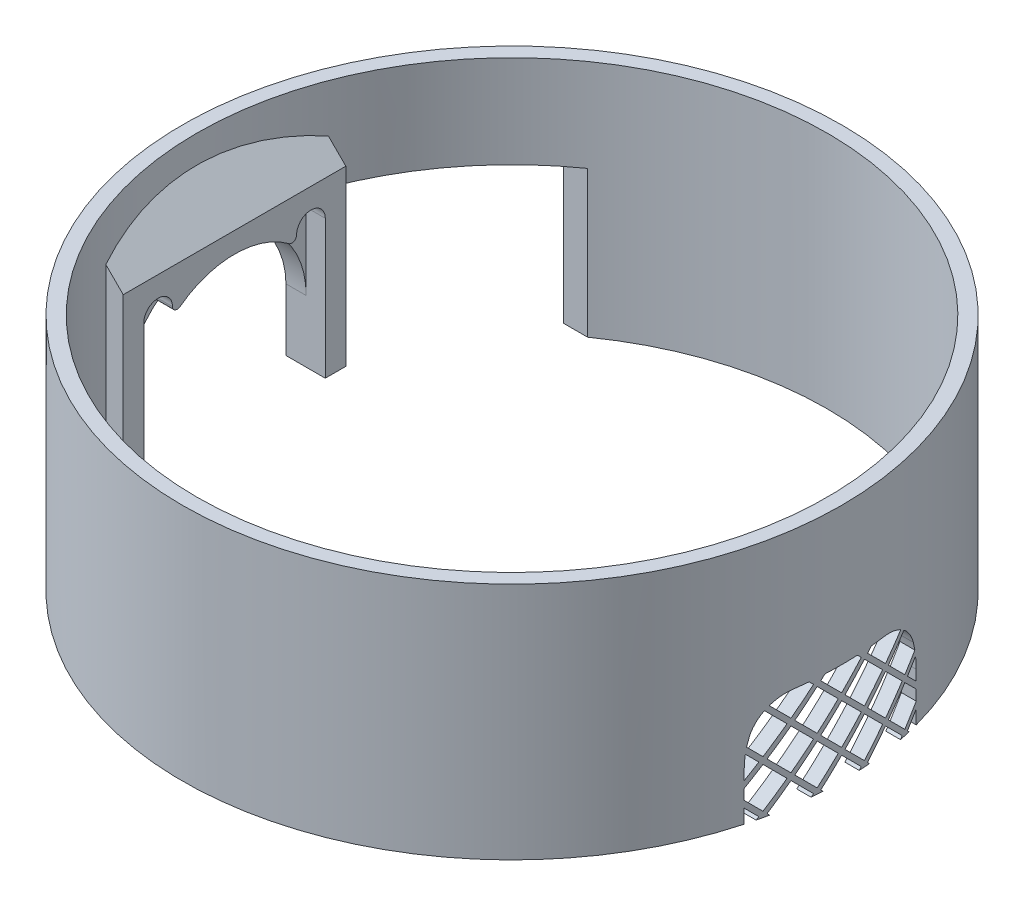
SolidWorks part; units mm, degrees
ref_plane "Front Plane" through (0, 0, 0) normal (0, 0, 1) x (1, 0, 0)
ref_plane "Top Plane" through (0, 0, 0) normal (0, 1, 0) x (1, 0, 0)
ref_plane "Right Plane" through (0, 0, 0) normal (1, 0, 0) x (0, 0, -1)
sketch "Sketch1" plane through (0, 0, 0) normal (0, 1, 0) x (1, 0, 0)
  circle A0 centre (0, 0) radius 69
  circle A1 centre (0, 0) radius 66
  dimension "D1" = 138
  dimension "D2" = 3
extrude "Boss-Extrude1" add sketch "Sketch1" along normal blind 50
sketch "Sketch4" plane through (0, 0, 0) normal (1, 0, 0) x (0, 0, -1)
  line L1 (23.3, 0) -> (53.9, 0)
  line L2 (23.3, 0) -> (23.3, 30.6)
  line L3 (23.3, 30.6) -> (53.9, 30.6)
  line L4 (53.9, 0) -> (53.9, 30.6)
  dimension "D1" = 30.6
  dimension "D2" = 30.6
  dimension "D3" = 0
  dimension "D4" = 23.3
extrude "Cut-Extrude2" cut sketch "Sketch4" against normal through all
sketch "Sketch5" plane through (0, 0, 0) normal (1, 0, 0) x (0, 0, -1)
  line L8 (19, 13) -> (19, -6)
  line L9 (19, -6) -> (-19, -6)
  line L10 (-19, -6) -> (-19, 13)
  arc A1 (19, 13) -> (-19, 13) centre (0, 13) ccw
  dimension "D1" = 19
  dimension "D3" = 13
  dimension "D2" = 19
extrude "Cut-Extrude6" cut sketch "Sketch5" against normal through all
sketch "Sketch6" plane through (0, 0, 0) normal (1, 0, 0) x (0, 0, -1)
  line L0 (19, 13) -> (19, 0)
  line L2 (-19, 0) -> (-19, 13)
  line L3 (23.3, 13) -> (23.3, 0)
  line L4 (-23.3, 0) -> (-23.3, 13)
  line L5 (23.3, 0) -> (19, 0)
  line L6 (-19, 0) -> (-23.3, 0)
  arc A0 (19, 13) -> (-19, 13) centre (0, 13) ccw
  arc A1 (23.3, 13) -> (-23.3, 13) centre (0, 13) ccw
  dimension "D1" = 19
  dimension "D3" = 0
  dimension "D2" = 4.3
extrude "Boss-Extrude2" add sketch "Sketch6" against normal up to next from offset 58.1 offset against normal yes
sketch "Sketch7" plane through (-58.1, 0, 0) normal (1, 0, 0) x (0, 0, -1)
  line L0 (0, 36.3) -> (15, 36.3) construction
  arc A0 (23.3, 13) -> (-23.3, 13) centre (0, 13) ccw construction
  dimension "D1" = 15
ref_plane "Plane2" through (-10.9, -10.9, 0) normal (-0.7071, -0.7071, 0) x (0, 0, -1)
sketch "Sketch8" plane through (-10.9, -10.9, 0) normal (-0.7071, -0.7071, 0) x (0, 0, -1)
  line L0 (23.3, -41.0829) -> (23.3, -50.2753) construction
  line L1 (-23.3, -84.0829) -> (23.3, -84.0829)
  line L2 (-23.3, -84.0829) -> (-23.3, -49.0829)
  line L3 (-23.3, -49.0829) -> (23.3, -49.0829)
  line L4 (23.3, -84.0829) -> (23.3, -49.0829)
  line L5 (-23.3, -50.2753) -> (-23.3, -41.0829) construction
  line L6 (19, -41.0829) -> (23.3, -41.0829) construction
  dimension "D1" = 0
  dimension "D2" = 0
  dimension "D3" = 8
  dimension "D4" = 35
extrude "Boss-Extrude4" add sketch "Sketch8" along normal blind 30 contours L2 L1 L4 L3
sketch "Sketch9" plane through (0, 0, 0) normal (0, -1, 0) x (1, 0, 0)
  line L0 (-58.1, -23.3) -> (-61.7504, -23.3)
  line L1 (-64.947, -23.3) -> (-58.1, -23.3) construction
  line L6 (-38.0892, -53.9) -> (-43.0789, -53.9)
  line L7 (-38.0892, -53.9) -> (-43.0789, -53.9)
  line L12 (-66.3325, 19) -> (-58.1, 19)
  line L14 (-58.1, 19) -> (-58.1, 23.3)
  line L15 (-58.1, 23.3) -> (-61.7504, 23.3)
  line L18 (-58.1, 19) -> (-58.1, 23.3)
  line L19 (-58.1, 23.3) -> (-61.7504, 23.3)
  line L20 (-58.1, 19) -> (-58.1, -19)
  line L24 (-58.1, -19) -> (-66.3325, -19)
  line L25 (-64.947, -23.3) -> (-58.1, -23.3)
  line L27 (-58.1, -23.3) -> (-58.1, -19)
  line L31 (-58.1, -23.3) -> (-58.1, -19)
  arc A6 (-43.0789, -53.9) -> (-66.3325, 19) centre (0, 0) ccw
  arc A7 (-38.0892, -53.9) -> (-61.7504, 23.3) centre (0, 0) ccw
  arc A8 (-43.0789, -53.9) -> (-66.3325, 19) centre (0, 0) ccw
  arc A9 (-38.0892, -53.9) -> (-61.7504, 23.3) centre (0, 0) ccw
  arc A10 (-66.3325, -19) -> (-66.3325, 19) centre (0, 0) ccw
  arc A11 (-61.7504, -23.3) -> (-61.7504, 23.3) centre (0, 0) ccw
  arc A12 (-66.3325, -19) -> (-64.947, -23.3) centre (0, 0) ccw
  arc A14 (-66.3325, -19) -> (-64.947, -23.3) centre (0, 0) ccw
  circle A16 centre (0, 0) radius 69
  arc A18 (-61.7504, -23.3) -> (-61.7504, 23.3) centre (0, 0) ccw
  line M15 (-66.3325, 19) -> (-58.1, 19)
  line M16 (-58.1, 19) -> (-58.1, 23.3)
  line M17 (-58.1, 23.3) -> (-61.7504, 23.3)
  arc M18 (-61.7504, 23.3) -> (-38.0892, -53.9) centre (0, 0) cw
  dimension "D1" = 0
  dimension "D2" = 0
extrude "Cut-Extrude7" cut sketch "Sketch9" against normal through all flip side to cut contours A16
extrude "Cut-Extrude8" cut sketch "Sketch9<3>" against normal through all contours L31 A11 M15 M18 M17 M16 region at (1.3919, 0, 0)
sketch "Sketch9<3>" plane through (0, 0, 0) normal (0, -1, 0) x (1, 0, 0) same geometry as "Sketch9"
extrude "Cut-Extrude9" cut sketch "Sketch5<2>" against normal through all
sketch "Sketch5<2>" plane through (0, 0, 0) normal (1, 0, 0) x (0, 0, -1) same geometry as "Sketch5"
sketch "Sketch11" plane through (-58.1, 0, 0) normal (1, 0, 0) x (0, 0, -1)
  line L0 (-19, 29) -> (-19, 11)
  line L1 (-19, 0) -> (-19, 13) construction
  line L2 (-19, 11) -> (-13, 11)
  line L3 (-13, 11) -> (-13, 29)
  line L4 (13, 29) -> (13, 11)
  line L5 (19, 29) -> (19, 11)
  line L6 (19, 13) -> (19, 0) construction
  line L7 (13, 11) -> (19, 11)
  arc A0 (19, 29) -> (13, 29) centre (16, 29) ccw
  arc A1 (-13, 29) -> (-19, 29) centre (-16, 29) ccw
  dimension "D1" = 6
  dimension "D2" = 6
  dimension "D3" = 18
  dimension "D4" = 18
extrude "Cut-Extrude11" cut sketch "Sketch11" against normal blind 4
fillet "Fillet3" radius 1 2 edges at (-60.1, 26.8564, -13) (-60.1, 26.8564, 13)
sketch "Sketch12" plane through (0, 0, 0) normal (1, 0, 0) x (0, 0, -1)
  line L0 (0, -0.9) -> (0, 0) construction
  line L1 (-69, 0) -> (69, 0) construction
  line L25 (-18, -0.9) -> (18, -0.9)
  line L28 (18, -0.9) -> (18, 10.1)
  line L29 (9.5394, 21.1) -> (-9.5394, 21.1)
  line L30 (-18, 10.1) -> (-18, -0.9)
  line L31 (18, -0.9) -> (18, 10.1)
  line L32 (9.5394, 21.1) -> (-9.5394, 21.1)
  line L33 (-18, 10.1) -> (-18, -0.9)
  line L51 (14.2005, -0.9) -> (14.8492, -0.2513)
  line L52 (14.8492, -0.2513) -> (15.498, -0.9)
  line L54 (16.9122, -0.9) -> (15.5563, 0.4558)
  line L55 (15.5563, 0.4558) -> (18, 2.8995)
  line L71 (4.301, -0.9) -> (4.9497, -0.2513)
  line L72 (4.9497, -0.2513) -> (5.5985, -0.9)
  line L73 (14.1421, 0.4558) -> (12.7863, -0.9)
  line L74 (7.0127, -0.9) -> (5.6569, 0.4558)
  line L75 (5.6569, 0.4558) -> (9.8995, 4.6985)
  line L76 (9.8995, 4.6985) -> (14.1421, 0.4558)
  line L77 (18, 4.3137) -> (14.8492, 1.163)
  line L78 (14.8492, 1.163) -> (10.6066, 5.4056)
  line L79 (10.6066, 5.4056) -> (14.8492, 9.6482)
  line L80 (14.8492, 9.6482) -> (18, 6.4975)
  line L82 (18, 7.9117) -> (15.5563, 10.3553)
  line L83 (15.5563, 10.3553) -> (17.8225, 12.6215)
  line L91 (-5.5985, -0.9) -> (-4.9497, -0.2513)
  line L92 (-4.9497, -0.2513) -> (-4.301, -0.9)
  line L93 (4.2426, 0.4558) -> (2.8868, -0.9)
  line L94 (-2.8868, -0.9) -> (-4.2426, 0.4558)
  line L95 (-4.2426, 0.4558) -> (0, 4.6985)
  line L96 (0, 4.6985) -> (4.2426, 0.4558)
  line L97 (9.1924, 5.4056) -> (4.9497, 1.163)
  line L98 (4.9497, 1.163) -> (0.7071, 5.4056)
  line L99 (0.7071, 5.4056) -> (4.9497, 9.6482)
  line L100 (4.9497, 9.6482) -> (9.1924, 5.4056)
  line L101 (14.1421, 10.3553) -> (9.8995, 6.1127)
  line L102 (9.8995, 6.1127) -> (5.6569, 10.3553)
  line L103 (5.6569, 10.3553) -> (9.8995, 14.598)
  line L104 (9.8995, 14.598) -> (14.1421, 10.3553)
  line L105 (17.6106, 13.8238) -> (14.8492, 11.0624)
  line L106 (14.8492, 11.0624) -> (10.6066, 15.3051)
  line L107 (10.6066, 15.3051) -> (14.5986, 19.2971)
  line L111 (-15.498, -0.9) -> (-14.8492, -0.2513)
  line L112 (-14.8492, -0.2513) -> (-14.2005, -0.9)
  line L113 (-5.6569, 0.4558) -> (-7.0127, -0.9)
  line L114 (-12.7863, -0.9) -> (-14.1421, 0.4558)
  line L115 (-14.1421, 0.4558) -> (-9.8995, 4.6985)
  line L116 (-9.8995, 4.6985) -> (-5.6569, 0.4558)
  line L117 (-0.7071, 5.4056) -> (-4.9497, 1.163)
  line L118 (-4.9497, 1.163) -> (-9.1924, 5.4056)
  line L119 (-9.1924, 5.4056) -> (-4.9497, 9.6482)
  line L120 (-4.9497, 9.6482) -> (-0.7071, 5.4056)
  line L121 (4.2426, 10.3553) -> (0, 6.1127)
  line L122 (0, 6.1127) -> (-4.2426, 10.3553)
  line L123 (-4.2426, 10.3553) -> (0, 14.598)
  line L124 (0, 14.598) -> (4.2426, 10.3553)
  line L125 (9.1924, 15.3051) -> (4.9497, 11.0624)
  line L126 (4.9497, 11.0624) -> (0.7071, 15.3051)
  line L127 (0.7071, 15.3051) -> (4.9497, 19.5477)
  line L128 (4.9497, 19.5477) -> (9.1924, 15.3051)
  line L129 (13.7744, 19.8871) -> (9.8995, 16.0122)
  line L130 (9.8995, 16.0122) -> (5.6569, 20.2548)
  line L131 (5.6569, 20.2548) -> (6.502, 21.1)
  line L133 (-15.5563, 0.4558) -> (-16.9122, -0.9)
  line L136 (-18, 2.8995) -> (-15.5563, 0.4558)
  line L137 (-10.6066, 5.4056) -> (-14.8492, 1.163)
  line L138 (-14.8492, 1.163) -> (-18, 4.3137)
  line L139 (-18, 6.4975) -> (-14.8492, 9.6482)
  line L140 (-14.8492, 9.6482) -> (-10.6066, 5.4056)
  line L141 (-5.6569, 10.3553) -> (-9.8995, 6.1127)
  line L142 (-9.8995, 6.1127) -> (-14.1421, 10.3553)
  line L143 (-14.1421, 10.3553) -> (-9.8995, 14.598)
  line L144 (-9.8995, 14.598) -> (-5.6569, 10.3553)
  line L145 (-0.7071, 15.3051) -> (-4.9497, 11.0624)
  line L146 (-4.9497, 11.0624) -> (-9.1924, 15.3051)
  line L147 (-9.1924, 15.3051) -> (-4.9497, 19.5477)
  line L148 (-4.9497, 19.5477) -> (-0.7071, 15.3051)
  line L149 (4.2426, 20.2548) -> (0, 16.0122)
  line L150 (0, 16.0122) -> (-4.2426, 20.2548)
  line L151 (-4.2426, 20.2548) -> (-3.3975, 21.1)
  line L152 (3.3975, 21.1) -> (4.2426, 20.2548)
  line L153 (5.0878, 21.1) -> (4.9497, 20.9619)
  line L154 (4.9497, 20.9619) -> (4.8117, 21.1)
  line L161 (-15.5563, 10.3553) -> (-18, 7.9117)
  line L164 (-17.8225, 12.6215) -> (-15.5563, 10.3553)
  line L165 (-10.6066, 15.3051) -> (-14.8492, 11.0624)
  line L166 (-14.8492, 11.0624) -> (-17.6106, 13.8238)
  line L168 (-14.5986, 19.2971) -> (-10.6066, 15.3051)
  line L169 (-5.6569, 20.2548) -> (-9.8995, 16.0122)
  line L170 (-9.8995, 16.0122) -> (-13.7744, 19.8871)
  line L172 (-6.502, 21.1) -> (-5.6569, 20.2548)
  line L173 (-4.8117, 21.1) -> (-4.9497, 20.9619)
  line L174 (-4.9497, 20.9619) -> (-5.0878, 21.1)
  arc A34 (18, 10.1) -> (17.1709, 15.5) centre (0, 10.1) ccw
  arc A35 (17.1709, 15.5) -> (9.5394, 21.1) centre (9.5394, 13.1) ccw
  arc A36 (-9.5394, 21.1) -> (-17.1709, 15.5) centre (-9.5394, 13.1) ccw
  arc A37 (-17.1709, 15.5) -> (-18, 10.1) centre (0, 10.1) ccw
  arc A38 (18, 10.1) -> (17.1709, 15.5) centre (0, 10.1) ccw
  arc A39 (17.1709, 15.5) -> (9.5394, 21.1) centre (9.5394, 13.1) ccw
  arc A40 (-9.5394, 21.1) -> (-17.1709, 15.5) centre (-9.5394, 13.1) ccw
  arc A41 (-17.1709, 15.5) -> (-18, 10.1) centre (0, 10.1) ccw
  dimension "D1" = 0
extrude "Cut-Extrude13" cut sketch "Sketch12" along normal through all contours L144 L143 L142 L141 | L148 L147 L146 L145 | A40 A41 L166 L165 L168 | L32 A40 L170 L169 L172 | L164 A41 L33 L161 | L140 L139 L33 L138 L137 | L136 L33 L25 L133 | L112 L111 L25 | L116 L115 L114 L25 L113 | L120 L119 L118 L117 | L96 L95 L94 L25 L93 | L92 L91 L25 | L124 L123 L122 L121 | L128 L127 L126 L125 | L152 L32 L151 L150 L149 | L129 A39 L32 L131 L130 | A38 A39 L107 L106 L105 | L104 L103 L102 L101 | L100 L99 L98 L97 | L76 L75 L74 L25 L73 | L80 L79 L78 L77 L31 | L31 A38 L83 L82 | L55 L54 L25 L31 | L52 L51 L25 | L72 L71 L25 region at (0, 0.6448, 17.1357) region at (0, -0.6838, 14.8492) region at (0, 5.4056, 14.7289) region at (0, 1.1541, 9.8995) region at (0, 10.3071, 17.1639) region at (0, -0.6838, 4.9497) region at (0, 15.1515, 14.4564) region at (0, 1.1541, 0) region at (0, -0.6838, -4.9497) region at (0, 19.2207, 9.6883) region at (0, 1.1541, -9.8995) region at (0, -0.6838, -14.8492) region at (0, 19.3215, 0) region at (0, 0.6448, -17.1357) region at (0, 5.4056, -14.7289) region at (0, 19.2207, -9.6883) region at (0, 10.3071, -17.1639) region at (0, 15.1515, -14.4564) region at (0, 5.4056, -4.9497) region at (0, 10.3553, -9.8995) region at (0, 5.4056, 4.9497) region at (0, 10.3553, 0) region at (0, 15.3051, -4.9497) region at (0, 10.3553, 9.8995) region at (0, 15.3051, 4.9497)
